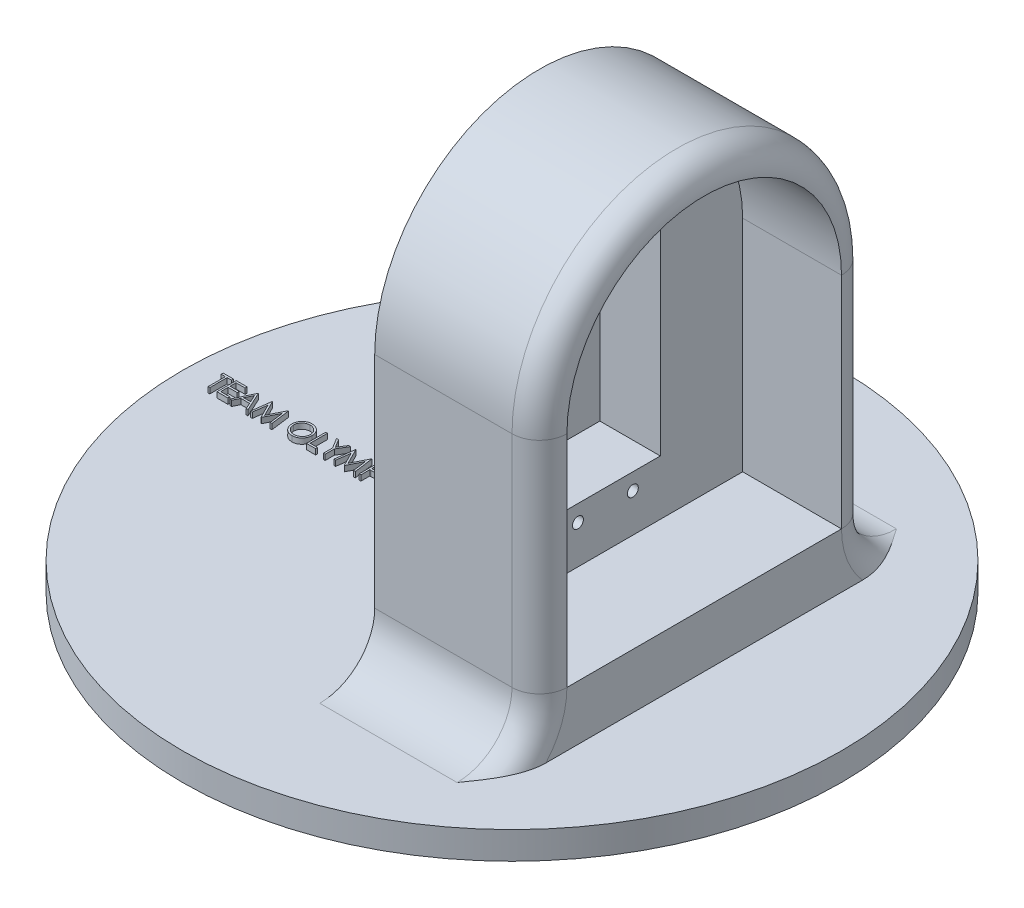
SolidWorks part; units mm, degrees
ref_plane "Front Plane" through (0, 0, 0) normal (0, 0, 1) x (1, 0, 0)
ref_plane "Top Plane" through (0, 0, 0) normal (0, 1, 0) x (1, 0, 0)
ref_plane "Right Plane" through (0, 0, 0) normal (1, 0, 0) x (0, 0, -1)
sketch "Sketch1" plane through (0, 0, 0) normal (0, 1, 0) x (1, 0, 0)
  circle A0 centre (0, 0) radius 60
  dimension "D1" = 120
extrude "Boss-Extrude1" add sketch "Sketch1" along normal blind 5
ref_plane "Plane1" through (5, 0, 0) normal (1, 0, 0) x (0, 0, -1)
sketch "Sketch3" plane through (5, 0, 0) normal (1, 0, 0) x (0, 0, -1)
  line L0 (60, 5) -> (-60, 5) construction
  line L1 (-30, 5) -> (30, 5)
  line L2 (-30, 5) -> (-30, 55)
  line L4 (30, 5) -> (30, 55)
  line L5 (60, 0) -> (60, 5) construction
  arc A0 (30, 55) -> (-30, 55) centre (0, 55) ccw
  dimension "D4" = 30
  dimension "D1" = 50
  dimension "D2" = 60
  dimension "D3" = 30
extrude "Boss-Extrude2" add sketch "Sketch3" along normal blind 30
fillet "Fillet1" radius 10 1 edges at (20, 5, -30)
fillet "Fillet2" radius 10 1 edges at (20, 5, 30)
fillet "Fillet3" radius 5 5 edges at (35, 7.9289, -32.9289) (35, 35, -30) (35, 7.9289, 32.9289) (35, 35, 30) (35, 85, 0)
ref_plane "Plane2" through (35, 0, 0) normal (1, 0, 0) x (0, 0, -1)
sketch "Sketch4" plane through (35, 0, 0) normal (1, 0, 0) x (0, 0, -1)
  line L0 (25, 15) -> (25, 55) construction
  line L1 (-10, 65) -> (10, 65)
  line L2 (-10, 65) -> (-10, 25)
  line L3 (-10, 25) -> (10, 25)
  line L4 (10, 65) -> (10, 25)
  line L5 (-10, 65) -> (10, 25) construction
  line L6 (-10, 25) -> (10, 65) construction
  arc A0 (30, 55) -> (-30, 55) centre (0, 55) ccw construction
  point P0 (0, 45)
  point P10 (0, 85)
  dimension "D1" = 40
  dimension "D2" = 20
  dimension "D3" = 15
  dimension "D4" = 40
extrude "Cut-Extrude1" cut sketch "Sketch4" against normal blind 29
sketch "Sketch6" plane through (35, 0, 0) normal (1, 0, 0) x (0, 0, -1)
  line L2 (-25, 55) -> (-25, 15)
  line L3 (-25, 15) -> (25, 15)
  line L4 (25, 55) -> (25, 15)
  arc A0 (-25, 55) -> (25, 55) centre (0, 55) cw
extrude "Cut-Extrude2" cut sketch "Sketch6" against normal blind 18
sketch "Sketch7" plane through (17, 0, 0) normal (1, 0, 0) x (0, 0, -1)
  line L0 (10, 25) -> (10, 65) construction
  line L1 (-10, 25) -> (10, 25) construction
  line L2 (-10, 65) -> (-10, 25) construction
  line L3 (10, 65) -> (-10, 65) construction
  circle A0 centre (5, 68) radius 1
  circle A1 centre (-5, 68) radius 1
  circle A2 centre (5, 22) radius 1
  circle A3 centre (-5, 22) radius 1
  dimension "D1" = 2
  dimension "D2" = 2
  dimension "D3" = 10
  dimension "D5" = 5
  dimension "D6" = 2
  dimension "D7" = 2
  dimension "D8" = 3
  dimension "D9" = 3
  dimension "D10" = 3
  dimension "D4" = 5
extrude "Cut-Extrude3" cut sketch "Sketch7" against normal blind 10
ref_plane "Plane3" through (0, 0, 0) normal (0, -1, 0) x (-1, 0, 0)
sketch "Sketch8" plane through (0, 0, 0) normal (0, -1, 0) x (-1, 0, 0)
  circle A0 centre (0, 0) radius 4
  circle A1 centre (0, -8) radius 1.5
  circle A2 centre (0, 8) radius 1.5
  dimension "D1" = 3
  dimension "D2" = 3
  dimension "D3" = 8
  dimension "D4" = 8
  dimension "D5" = 8
extrude "Cut-Extrude4" cut sketch "Sketch8" against normal blind 20
sketch "Sketch9" plane through (35, 0, 0) normal (1, 0, 0) x (0, 0, -1)
  circle A0 centre (0, 55.5078) radius 9.3784
extrude "Cut-Extrude5" cut sketch "Sketch9" against normal blind 40
ref_plane "Plane4" through (0, 5, 0) normal (0, 1, 0) x (1, 0, 0)
sketch "Sketch10" plane through (0, 5, 0) normal (0, 1, 0) x (1, 0, 0)
  text T0 "TEAM OLYMPUS 2023"
extrude "Boss-Extrude3" add sketch "Sketch10" along normal blind 1
